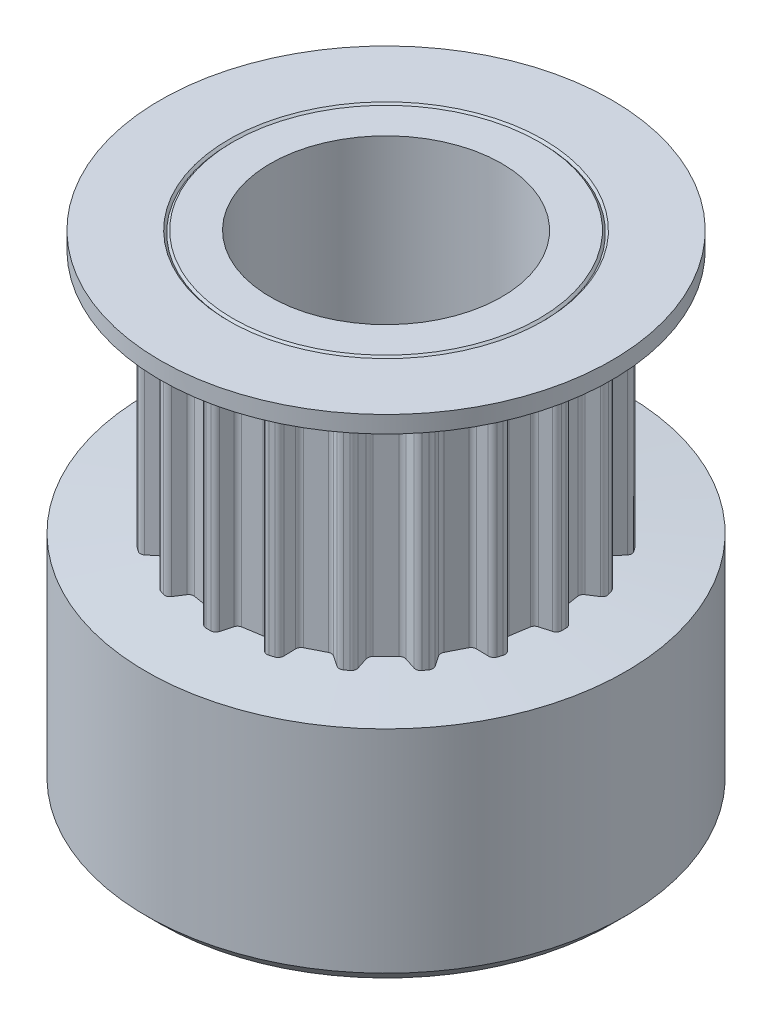
SolidWorks part; units mm, degrees
material "1060 Alloy"
ref_plane "Front Plane" through (0, 0, 0) normal (0, 0, 1) x (1, 0, 0)
ref_plane "Top Plane" through (0, 0, 0) normal (0, 1, 0) x (1, 0, 0)
ref_plane "Right Plane" through (0, 0, 0) normal (1, 0, 0) x (0, 0, -1)
ref_axis "Rotation Axis" through (0, -0.9, 0) along (0, 1, 0)
sketch "Sketch1" plane through (0, 0, 0) normal (1, 0, 0) x (0, 0, -1)
  line L0 (0, -99.3084) -> (0, 91.325) construction
  line L1 (4.1, -8.65) -> (4.1, 8.65)
  line L2 (8.5, -8.15) -> (8.5, -0.65)
  line L3 (8, -8.65) -> (8.5, -8.15)
  line L4 (8.5, -0.65) -> (5.5, -0.3875)
  line L5 (5.5, 7.8313) -> (8, 8.05)
  line L6 (8, 8.05) -> (8, 8.65)
  line L7 (8, 8.65) -> (5.575, 8.65)
  line L8 (4.1, -8.65) -> (8, -8.65)
  line L9 (5.5, 7.8313) -> (5.5, -0.3875)
  line L10 (5.425, 8.65) -> (5.5, 8.575)
  line L11 (5.5, 8.575) -> (5.575, 8.65)
  line L12 (5.425, 8.65) -> (4.1, 8.65)
  line L13 (4.1, 0) -> (0, 0) construction
  dimension "D2" = 11
  dimension "D3" = 16
  dimension "D4" = 8.7
  dimension "D5" = 0.5
  dimension "D6" = 0.5
  dimension "D7" = 0.6
  dimension "D8" = 8.2
  dimension "D9" = 17.3
  dimension "D10" = 95
  dimension "D11" = 95
  dimension "D12" = 17
  dimension "D13" = 11
  dimension "D14" = 0.15
revolve "Profile" add sketch "Sketch1" angle 360 about L0
ref_plane "Tooth Mid Plane" through (0, 3.7, 0) normal (0, 1, 0) x (1, 0, 0)
sketch "Sketch5" plane through (0, 3.7, 0) normal (0, -1, 0) x (-1, 0, 0)
  line L0 (-0.5655, 5.6815) -> (-1.2178, 5.5782)
  line L1 (-0.2705, 6.1711) -> (-0.4101, 5.8073)
  line L2 (0.4101, 5.8073) -> (0.2705, 6.1711)
  line L3 (-0.5655, 5.6815) -> (0, 0) construction
  line L4 (0, 0) -> (0.5655, 5.6815) construction
  line L5 (-0.0838, 6.0994) -> (0.0838, 6.0994) construction
  line L6 (-0.5968, 5.879) -> (0.5968, 5.879) construction
  line L7 (-0.3403, 5.9892) -> (0.3403, 5.9892) construction
  line L8 (0, 6.3) -> (0, 6.0994) construction
  line L9 (0, 6.0994) -> (0, 5.9892) construction
  line L10 (0, 5.9892) -> (0, 5.879) construction
  line L11 (0.5655, 5.6815) -> (-0.5655, 5.6815) construction
  line L12 (1.2178, 5.5782) -> (0.5655, 5.6815) construction
  line L13 (0, 5.8073) -> (0, 5.7096) construction
  line L14 (0, 5.7096) -> (0, 5.6815) construction
  line L15 (0, 5.6815) -> (0, 5.5782) construction
  line L16 (-0.4101, 5.8073) -> (0.4101, 5.8073) construction
  line L17 (0, 5.8073) -> (0, 5.879) construction
  line L18 (1.2178, 5.5782) -> (-1.2178, 5.5782) construction
  line L19 (0, 5.5782) -> (0, 0) construction
  line L20 (-0.8917, 5.6298) -> (0, 0) construction
  line L21 (0, 0) -> (0.8917, 5.6298) construction
  line L22 (1.2178, 5.5782) -> (0, 0) construction
  line L23 (0, 0) -> (-1.2178, 5.5782) construction
  line L24 (-1.2178, 5.5782) -> (-1.0665, 4.8849)
  line L25 (0.5655, 5.6815) -> (0.4952, 4.9754)
  line L26 (-0.4101, 5.8073) -> (-0.4546, 5.6914) construction
  line L28 (0.4101, 5.8073) -> (0.4546, 5.6914) construction
  arc A0 (-0.5655, 5.6815) -> (-0.4101, 5.8073) centre (-0.5968, 5.879) ccw
  arc A1 (-0.0865, 6.2994) -> (-0.2705, 6.1711) centre (-0.0838, 6.0994) ccw
  arc A2 (0.0865, 6.2994) -> (-0.0865, 6.2994) centre (0, 0) ccw
  arc A3 (0.2705, 6.1711) -> (0.0865, 6.2994) centre (0.0838, 6.0994) ccw
  arc A4 (0.4101, 5.8073) -> (0.5655, 5.6815) centre (0.5968, 5.879) ccw
  arc A5 (-1.2178, 5.5782) -> (1.2178, 5.5782) centre (0, 0) cw construction
  arc A6 (-1.0665, 4.8849) -> (0.4952, 4.9754) centre (0, 0) cw
  dimension "D3" = 0.2
  dimension "D4" = 18
  dimension "D1" = 6.3
  dimension "D2" = 5.7
  dimension "D6" = 5
  dimension "D5" = 42
  dimension "D7" = 0.1675
extrude "Tooth" add sketch "Sketch5" along normal mid plane 8.7
pattern_circular "Tooth Pattern" count 20 over 360 about axis through (0, -0.9, 0) along (0, 1, 0) of "Tooth"
ref_plane "Setscrew Plane" through (0, 0, -8.5) normal (0, 0, -1) x (-1, 0, 0)
sketch "Setscrew Point" plane through (0, 0, -8.5) normal (0, 0, -1) x (-1, 0, 0)
  line L0 (0, -0.65) -> (0, -8.65) construction
  line L1 (-8.5, -0.65) -> (8.5, -0.65) construction
  line L2 (-8, -8.65) -> (8, -8.65) construction
  point P5 (0, -4.65)
hole_wizard "M3x0.5 Setscew Hole" positions "Sketch8" profile "Sketch7" tap size "M3x0.5" standard "ANSI Metric" end condition up to next
sketch "Sketch8" plane through (0, 0, -8.5) normal (0, 0, -1) x (-1, 0, 0)
  point P0 (0, -4.65)
sketch "Sketch7" plane through (0, -4.65, -8.5) normal (1, 0, 0) x (0, 1, 0)
  line L0 (0, 0) -> (0, 4.4)
  line L1 (0, 4.4) -> (1.25, 4.4)
  line L2 (1.25, 4.4) -> (1.25, 0)
  line L3 (4, 17) -> (-3.5, 17) construction
  line L4 (-3.5, 0) -> (4, 0) construction
  line L5 (1.25, 0) -> (0, 0)
  line L11 (0, 0) -> (0, 17) construction
  dimension "Thru Tap Drill Dia." = 2.5
  dimension "Thru Tap Drill Depth" = 4.4
cosmetic thread "Hole Thread1" parameters "D2"=3
